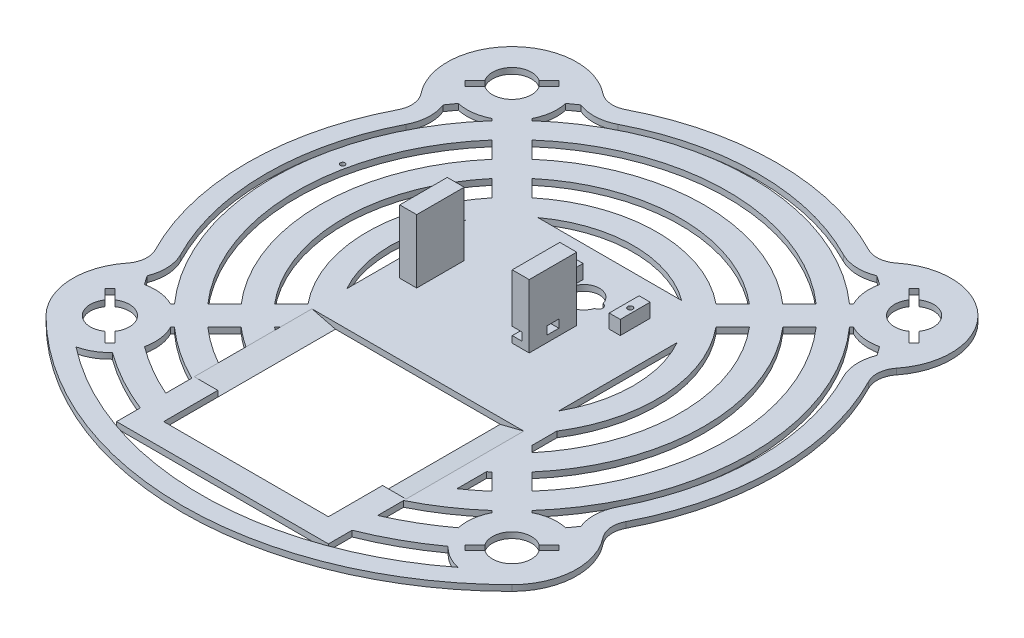
SolidWorks part; units mm, degrees
note: The reader was unsure of these and kept them because the rebuilt part matched: shared geometry of "Çizim4<3>", "Çizim5<3>".
ref_plane "Ön Düzlem" through (0, 0, 0) normal (0, 0, 1) x (1, 0, 0)
ref_plane "Üst Düzlem" through (0, 0, 0) normal (0, 1, 0) x (1, 0, 0)
ref_plane "Sağ Düzlem" through (0, 0, 0) normal (1, 0, 0) x (0, 0, -1)
sketch "Çizim1" plane through (0, 0, 0) normal (0, 1, 0) x (1, 0, 0)
  line L1 (-35, -40) -> (35, -40)
  line L2 (-35, -40) -> (-35, -113)
  line L3 (-35, -113) -> (35, -113)
  line L4 (35, -40) -> (35, -113)
  circle A0 centre (0, 0) radius 140
  point P7 (0, -40)
  dimension "D1" = 280
  dimension "D2" = 40
  dimension "D3" = 73
  dimension "D4" = 70
extrude "Yükseklik-Ekstrüzyon1" add sketch "Çizim1" along normal blind 2.5
sketch "Çizim2" plane through (0, 0, 0) normal (0, -1, 0) x (1, 0, 0)
  arc A2 (14.5208, -23.2542) -> (14.5208, -20.7458) centre (14.75, -22) ccw
  arc A3 (14.5208, -20.7458) -> (14.5208, -23.2542) centre (8.5, -22) ccw
  arc A4 (14.9108, -20.2323) -> (14.9108, -23.7677) centre (8.5, -22) ccw
  arc A5 (14.9108, -23.7677) -> (14.9108, -20.2323) centre (14.75, -22) ccw
  arc A9 (14.5208, -20.7458) -> (14.5208, -23.2542) centre (8.5, -22) ccw construction
  dimension "D4" = 6.15
  dimension "D2" = 6.25
  dimension "D3" = 2.5084
  dimension "D1" = 0.5
extrude "Kes-Ekstrüzyon1" cut sketch "Çizim2" against normal through all contours A2 A3 | A4 A5 A3 A2
sketch "Çizim3" plane through (0, 2.5, 0) normal (0, 1, 0) x (1, 0, 0)
  line L1 (-2.85, 28.35) -> (1.85, 28.35)
  line L2 (-2.85, 28.35) -> (-2.85, 15.65)
  line L3 (-2.85, 15.65) -> (1.85, 15.65)
  line L4 (1.85, 28.35) -> (1.85, 15.65)
  line L6 (30.35, 28.35) -> (25.65, 28.35)
  line L7 (30.35, 28.35) -> (30.35, 15.65)
  line L8 (30.35, 15.65) -> (25.65, 15.65)
  line L9 (25.65, 28.35) -> (25.65, 15.65)
  circle A2 centre (28.25, 22) radius 1.0925
  circle A3 centre (-0.75, 22) radius 1.1001
extrude "Yükseklik-Ekstrüzyon2" add sketch "Çizim3" along normal up to vertex (5.95 mm away)
sketch "Çizim4" plane through (0, 0, 0) normal (0, -1, 0) x (1, 0, 0)
  line L0 (35, 113) -> (35, 40) construction
  line L1 (35, 70.1054) -> (42, 70.1054)
  line L2 (35, 70.1054) -> (35, 40.1054)
  line L3 (35, 40.1054) -> (42, 40.1054)
  line L4 (42, 70.1054) -> (42, 40.1054)
  line L9 (38, 70.1054) -> (38, 40.1054)
  line M14 (35, 113) -> (35, 40)
  dimension "D1" = 7
  dimension "D2" = 4
  dimension "D3" = 30
extrude "Yükseklik-Ekstrüzyon3" add sketch "Çizim4" along normal blind 4 contours L1 L9 L3 L4
extrude "Yükseklik-Ekstrüzyon4" add sketch "Çizim4<3>" along normal blind 3 from surface at 4 contours L9 L1 L3 M14 | L1 L9 L3 L4 starting at face at (40, -4, 55.1054)
sketch "Çizim4<3>" plane through (0, 0, 0) normal (0, -1, 0) x (1, 0, 0) same geometry as "Çizim4"
sketch "Çizim5" plane through (0, 0, 0) normal (0, -1, 0) x (1, 0, 0)
  circle A0 centre (-21.1437, -10.4346) radius 3
  circle A2 centre (-21.1437, -10.4346) radius 5
  dimension "D1" = 6
  dimension "D2" = 2
extrude "Yükseklik-Ekstrüzyon5" add sketch "Çizim5" along normal up to surface (2.5 mm away) contours A0
extrude "Yükseklik-Ekstrüzyon6" add sketch "Çizim5<3>" along normal blind 2 from surface at 2.5
sketch "Çizim5<3>" plane through (0, 0, 0) normal (0, -1, 0) x (1, 0, 0) same geometry as "Çizim5"
sketch "Çizim6" plane through (0, 2.5, 0) normal (0, 1, 0) x (1, 0, 0)
  line L0 (-165.7847, 0) -> (170.866, 0) construction
  line L1 (0, 0) -> (145.0639, -145.0639) construction
  line L2 (85.4185, -85.4185) -> (105.6776, -65.1594) construction
  line L3 (90.1302, -78.5855) -> (92.2515, -80.7068)
  line L4 (90.1302, -78.5855) -> (94.3728, -74.3429)
  line L5 (94.3728, -74.3429) -> (96.4941, -76.4642)
  line L6 (92.2515, -80.7068) -> (96.4941, -76.4642)
  line L7 (80.7068, -92.2515) -> (76.4642, -96.4941)
  line L8 (74.3429, -94.3728) -> (76.4642, -96.4941)
  line L9 (78.5855, -90.1302) -> (74.3429, -94.3728)
  line L10 (78.5855, -90.1302) -> (80.7068, -92.2515)
  line L11 (-78.5855, -90.1302) -> (-74.3429, -94.3728)
  line L12 (-78.5855, -90.1302) -> (-80.7068, -92.2515)
  line L13 (-80.7068, -92.2515) -> (-76.4642, -96.4941)
  line L14 (-74.3429, -94.3728) -> (-76.4642, -96.4941)
  line L15 (-92.2515, -80.7068) -> (-96.4941, -76.4642)
  line L16 (-94.3728, -74.3429) -> (-96.4941, -76.4642)
  line L17 (-90.1302, -78.5855) -> (-94.3728, -74.3429)
  line L18 (-90.1302, -78.5855) -> (-92.2515, -80.7068)
  line L19 (-90.1302, 78.5855) -> (-94.3728, 74.3429)
  line L20 (-90.1302, 78.5855) -> (-92.2515, 80.7068)
  line L21 (-92.2515, 80.7068) -> (-96.4941, 76.4642)
  line L22 (-94.3728, 74.3429) -> (-96.4941, 76.4642)
  line L23 (-80.7068, 92.2515) -> (-76.4642, 96.4941)
  line L24 (-74.3429, 94.3728) -> (-76.4642, 96.4941)
  line L25 (-78.5855, 90.1302) -> (-74.3429, 94.3728)
  line L26 (-78.5855, 90.1302) -> (-80.7068, 92.2515)
  line L27 (78.5855, 90.1302) -> (74.3429, 94.3728)
  line L28 (78.5855, 90.1302) -> (80.7068, 92.2515)
  line L29 (80.7068, 92.2515) -> (76.4642, 96.4941)
  line L30 (74.3429, 94.3728) -> (76.4642, 96.4941)
  line L31 (92.2515, 80.7068) -> (96.4941, 76.4642)
  line L32 (94.3728, 74.3429) -> (96.4941, 76.4642)
  line L33 (90.1302, 78.5855) -> (94.3728, 74.3429)
  line L34 (90.1302, 78.5855) -> (92.2515, 80.7068)
  circle A0 centre (0, 0) radius 112.5
  circle A1 centre (85.4185, -85.4185) radius 8.3
  arc A2 (57.8732, -96.4725) -> (96.4725, -57.8732) centre (79.5495, -79.5495) ccw
  circle A3 centre (0, 0) radius 140 construction
  circle A4 centre (0, 0) radius 140
  arc A5 (-96.4725, -57.8732) -> (-57.8732, -96.4725) centre (-79.5495, -79.5495) ccw
  circle A6 centre (-85.4185, -85.4185) radius 8.3
  arc A7 (-57.8732, 96.4725) -> (-96.4725, 57.8732) centre (-79.5495, 79.5495) ccw
  circle A8 centre (-85.4185, 85.4185) radius 8.3
  arc A9 (96.4725, 57.8732) -> (57.8732, 96.4725) centre (79.5495, 79.5495) ccw
  circle A10 centre (85.4185, 85.4185) radius 8.3
  point P32 (0, 0)
  point P37 (95.4335, -75.4035)
  point P39 (91.1908, -79.6462)
  point P68 (0, 0)
  circle M7 centre (0, 0) radius 140
  dimension "D2" = 4
  dimension "D3" = 16.6
  dimension "D7" = 225
  dimension "D1" = 45
  dimension "D4" = 90
  dimension "D5" = 3
  dimension "D6" = 6
  dimension "D8" = 4
extrude "Kes-Ekstrüzyon2" cut sketch "Çizim6" against normal through all contours A9 A0 A2 M7 | A7 A4 A5 A0 | A9 A4 A7 A0 | A8 | L21 L22 L19 L20 | L25 L24 L23 L26 | A10 | L31 L32 L33 L34 | L29 L30 L27 L28 | A1 | L6 L5 L4 L3 | L7 L8 L9 L10 | A6 | L13 L14 L11 L12 | L15 L16 L17 L18
fillet "Radyus1" radius 10 6 edges at (-96.4725, 1.25, -57.8732) (-57.8732, 1.25, -96.4725) (-96.4725, 1.25, 57.8732) (96.4725, 1.25, 57.8732) (57.8732, 1.25, -96.4725) (96.4725, 1.25, -57.8732)
sketch "Çizim7" plane through (0, 2.5, 0) normal (0, 1, 0) x (1, 0, 0)
  line L1 (-30.3941, -10.1) -> (-37.5941, -10.1)
  line L2 (-30.3941, -10.1) -> (-30.3941, 10.1)
  line L3 (-30.3941, 10.1) -> (-37.5941, 10.1)
  line L4 (-37.5941, -10.1) -> (-37.5941, 10.1)
  line L8 (17.4059, -10.1) -> (10.2059, -10.1)
  line L9 (17.4059, -10.1) -> (17.4059, 10.1)
  line L10 (17.4059, 10.1) -> (10.2059, 10.1)
  line L11 (10.2059, -10.1) -> (10.2059, 10.1)
extrude "Yükseklik-Ekstrüzyon7" add sketch "Çizim7" along normal up to surface (27 mm away)
sketch "Çizim9" plane through (0, 0, 10.1) normal (0, 0, 1) x (1, 0, 0)
  line L0 (10.2059, 29.5) -> (10.2059, 2.5) construction
  line L1 (10.2059, 8.7) -> (14.4059, 8.7)
  line L2 (10.2059, 8.7) -> (10.2059, 5.3)
  line L3 (10.2059, 5.3) -> (14.4059, 5.3)
  line L4 (14.4059, 8.7) -> (14.4059, 5.3)
  line L7 (17.4059, 29.5) -> (17.4059, 2.5) construction
  dimension "D3" = 3
extrude "Kes-Ekstrüzyon3" cut sketch "Çizim9" against normal up to vertex (12.6 mm away)
sketch "Çizim10" plane through (17.4059, 0, 0) normal (1, 0, 0) x (0, 0, -1)
  line L0 (2.5, 8.7) -> (-10.1, 8.7) construction
  line L1 (-2.5731, 8.7) -> (2.5, 8.7)
  line L2 (-2.5731, 8.7) -> (-2.5731, 5.3)
  line L3 (-2.5731, 5.3) -> (2.5, 5.3)
  line L4 (2.5, 8.7) -> (2.5, 5.3)
  line L5 (2.5, 5.3) -> (-10.1, 5.3) construction
extrude "Kes-Ekstrüzyon4" cut sketch "Çizim10" against normal up to next
sketch "Çizim11" plane through (0, 0, 0) normal (0, -1, 0) x (1, 0, 0)
  circle A0 centre (-91.7272, -19.7572) radius 1
extrude "Kes-Ekstrüzyon5" cut sketch "Çizim11" against normal through all
sketch "Çizim12" plane through (0, 0, 0) normal (0, -1, 0) x (1, 0, 0)
  line L0 (35, 113) -> (35, 40) construction
  line L2 (-35, 113) -> (35, 113) construction
  line L3 (-35, 40) -> (-35, 113) construction
  line L5 (42, 40.1054) -> (35, 40.1054) construction
  line L6 (42, 40.1054) -> (42, 70.1054) construction
  line L7 (42, 70.1054) -> (35, 70.1054) construction
  line L8 (-35, 113) -> (35, 113)
  line L9 (-35, 40) -> (-35, 113)
  line L11 (42, 40.1054) -> (35, 40.1054)
  line L12 (42, 40.1054) -> (42, 70.1054)
  line L13 (35, 113) -> (35, 70.1054)
  line L14 (42, 70.1054) -> (35, 70.1054)
  line L15 (35, 40.1054) -> (35, 40)
  line L16 (-35, 40) -> (-35, -31.576)
  line L17 (-35, -31.576) -> (35, -31.576)
  line L18 (35, -31.576) -> (35, 40)
  line L19 (45, 30.1054) -> (45, 30.1054)
  line L20 (45, -41.576) -> (45, 30.1054)
  line L21 (-45, -41.576) -> (45, -41.576)
  line L22 (-45, 40) -> (-45, -41.576)
  line L23 (-45, 40) -> (-45, 123)
  line L24 (-45, 123) -> (45, 123)
  line L25 (45, 123) -> (45, 80.1054)
  line L26 (52, 80.1054) -> (45, 80.1054)
  line L27 (52, 30.1054) -> (52, 80.1054)
  line L28 (52, 30.1054) -> (45, 30.1054)
  line L29 (-150.2805, 141.7953) -> (-141.7953, 150.2805)
  line L30 (-150.2805, 141.7953) -> (118.1931, -126.6784)
  line L31 (-141.7953, 150.2805) -> (126.6784, -118.1931)
  line L32 (118.1931, -126.6784) -> (126.6784, -118.1931)
  line L33 (-146.0379, 146.0379) -> (122.4358, -122.4358) construction
  line L34 (-148.7514, -157.2367) -> (-157.2367, -148.7514)
  line L35 (-148.7514, -157.2367) -> (140.8822, 132.3969)
  line L36 (-157.2367, -148.7514) -> (132.3969, 140.8822)
  line L37 (140.8822, 132.3969) -> (132.3969, 140.8822)
  line L38 (-152.994, -152.994) -> (136.6396, 136.6396) construction
  arc A0 (-47.9125, -92.869) -> (47.9125, -92.869) centre (0, 0) ccw
  arc A1 (67.3897, -94.7938) -> (47.9125, -92.869) centre (56.1653, -108.8655) ccw
  arc A2 (67.3897, -94.7938) -> (94.7938, -67.3897) centre (79.5495, -79.5495) ccw
  arc A3 (92.869, -47.9125) -> (94.7938, -67.3897) centre (108.8655, -56.1653) ccw
  arc A4 (92.869, -47.9125) -> (92.869, 47.9125) centre (0, 0) ccw
  arc A5 (94.7938, 67.3897) -> (92.869, 47.9125) centre (108.8655, 56.1653) ccw
  arc A6 (94.7938, 67.3897) -> (93.3381, 93.3381) centre (79.5495, 79.5495) ccw
  arc A7 (93.3381, 93.3381) -> (-93.3381, 93.3381) centre (0, 0) ccw
  arc A8 (-93.3381, 93.3381) -> (-94.7938, 67.3897) centre (-79.5495, 79.5495) ccw
  arc A9 (-92.869, 47.9125) -> (-94.7938, 67.3897) centre (-108.8655, 56.1653) ccw
  arc A10 (-92.869, 47.9125) -> (-92.869, -47.9125) centre (0, 0) ccw
  arc A11 (-94.7938, -67.3897) -> (-92.869, -47.9125) centre (-108.8655, -56.1653) ccw
  arc A12 (-94.7938, -67.3897) -> (-67.3897, -94.7938) centre (-79.5495, -79.5495) ccw
  arc A13 (-47.9125, -92.869) -> (-67.3897, -94.7938) centre (-56.1653, -108.8655) ccw
  arc A14 (-51.5804, -99.9786) -> (51.5804, -99.9786) centre (0, 0) ccw
  arc A15 (62.4011, -101.0479) -> (51.5804, -99.9786) centre (56.1653, -108.8655) ccw
  arc A16 (62.4011, -101.0479) -> (101.0479, -62.4011) centre (79.5495, -79.5495) ccw
  arc A17 (99.9786, -51.5804) -> (101.0479, -62.4011) centre (108.8655, -56.1653) ccw
  arc A18 (99.9786, -51.5804) -> (99.9786, 51.5804) centre (0, 0) ccw
  arc A19 (101.0479, 62.4011) -> (99.9786, 51.5804) centre (108.8655, 56.1653) ccw
  arc A20 (101.0479, 62.4011) -> (98.9949, 98.9949) centre (79.5495, 79.5495) ccw
  arc A21 (98.9949, 98.9949) -> (-98.9949, 98.9949) centre (0, 0) ccw
  arc A22 (-98.9949, 98.9949) -> (-101.0479, 62.4011) centre (-79.5495, 79.5495) ccw
  arc A23 (-99.9786, 51.5804) -> (-101.0479, 62.4011) centre (-108.8655, 56.1653) ccw
  arc A24 (-99.9786, 51.5804) -> (-99.9786, -51.5804) centre (0, 0) ccw
  arc A25 (-101.0479, -62.4011) -> (-99.9786, -51.5804) centre (-108.8655, -56.1653) ccw
  arc A26 (-101.0479, -62.4011) -> (-62.4011, -101.0479) centre (-79.5495, -79.5495) ccw
  arc A27 (-51.5804, -99.9786) -> (-62.4011, -101.0479) centre (-56.1653, -108.8655) ccw
  arc A28 (-51.5804, -99.9786) -> (51.5804, -99.9786) centre (0, 0) ccw
  arc A29 (62.4011, -101.0479) -> (51.5804, -99.9786) centre (56.1653, -108.8655) ccw
  arc A30 (62.4011, -101.0479) -> (101.0479, -62.4011) centre (79.5495, -79.5495) ccw
  arc A31 (99.9786, -51.5804) -> (101.0479, -62.4011) centre (108.8655, -56.1653) ccw
  arc A32 (99.9786, -51.5804) -> (99.9786, 51.5804) centre (0, 0) ccw
  arc A33 (101.0479, 62.4011) -> (99.9786, 51.5804) centre (108.8655, 56.1653) ccw
  arc A34 (101.0479, 62.4011) -> (98.9949, 98.9949) centre (79.5495, 79.5495) ccw
  arc A35 (98.9949, 98.9949) -> (-98.9949, 98.9949) centre (0, 0) ccw
  arc A36 (-98.9949, 98.9949) -> (-101.0479, 62.4011) centre (-79.5495, 79.5495) ccw
  arc A37 (-99.9786, 51.5804) -> (-101.0479, 62.4011) centre (-108.8655, 56.1653) ccw
  arc A38 (-99.9786, 51.5804) -> (-99.9786, -51.5804) centre (0, 0) ccw
  arc A39 (-101.0479, -62.4011) -> (-99.9786, -51.5804) centre (-108.8655, -56.1653) ccw
  arc A40 (-101.0479, -62.4011) -> (-62.4011, -101.0479) centre (-79.5495, -79.5495) ccw
  arc A41 (-51.5804, -99.9786) -> (-62.4011, -101.0479) centre (-56.1653, -108.8655) ccw
  circle A42 centre (-85.4185, -85.4185) radius 19.2
  circle A43 centre (-85.4185, 85.4185) radius 19.2
  circle A44 centre (85.4185, 85.4185) radius 19.2
  circle A45 centre (85.4185, -85.4185) radius 19.2
  circle A46 centre (0, 0) radius 41.576
  circle A47 centre (0, 0) radius 51.576
  circle A48 centre (0, 0) radius 61.576
  circle A49 centre (0, 0) radius 71.576
  circle A50 centre (0, 0) radius 81.576
  circle A51 centre (0, 0) radius 91.576
  circle A52 centre (0, 0) radius 101.576
  circle A53 centre (0, 0) radius 111.576
  circle A54 centre (0, 0) radius 121.576
  dimension "D12" = 83.1519
  dimension "D17" = 12
  dimension "D18" = 12
  dimension "D1" = 0
  dimension "D2" = 8
  dimension "D3" = 10
  dimension "D4" = 10
  dimension "D5" = 10
  dimension "D6" = 10
  dimension "D7" = 10
  dimension "D8" = 10
  dimension "D9" = 10
  dimension "D10" = 10
  dimension "D11" = 10
extrude "Kes-Ekstrüzyon6" cut sketch "Çizim12" against normal through all contours L35 A49 L30 A48 | L35 A51 L30 A50 | L21 A47 | L20 A47 | A1 A53 A45 L30 A52 L35 A42 A13 A0 | A45 A53 A3 A4 A5 A44 L35 A52 L31 | L31 A51 L35 A50 | L31 A49 L35 L27 A48 | L22 A47 | L30 A49 L36 A48 | L30 A51 L36 A50 | A43 A53 A9 A10 A11 A42 L36 A52 L30 | L23 A53 A43 L31 A52 | L23 A51 L31 A50 | L23 A49 L31 | A44 A53 L25 A52 L36 | L36 A51 L25 L26 L27 A50 | A54 A44 A7 A43 L23 L24 L25
ref_plane "Düzlem1" through (0, 0, 40) normal (0, 0, 1) x (1, 0, 0)
sketch "Çizim13" plane through (0, 0, 40) normal (0, 0, 1) x (1, 0, 0)
  line L0 (-35, 0) -> (-35, 2.5)
  line L1 (-35, 2.5) -> (-45, 2.5)
  line L3 (-45, 2.5) -> (-35, 0)
  line L4 (35, 0) -> (35, 2.5)
  line L5 (35, 2.5) -> (45, 2.5)
  line L6 (-54.6764, 2.5) -> (-71.576, 2.5) construction
  line L7 (45, 2.5) -> (35, 0)
  dimension "D1" = 10
  dimension "D2" = 10
extrude "Kes-Ekstrüzyon7" cut sketch "Çizim13" along normal blind 50
